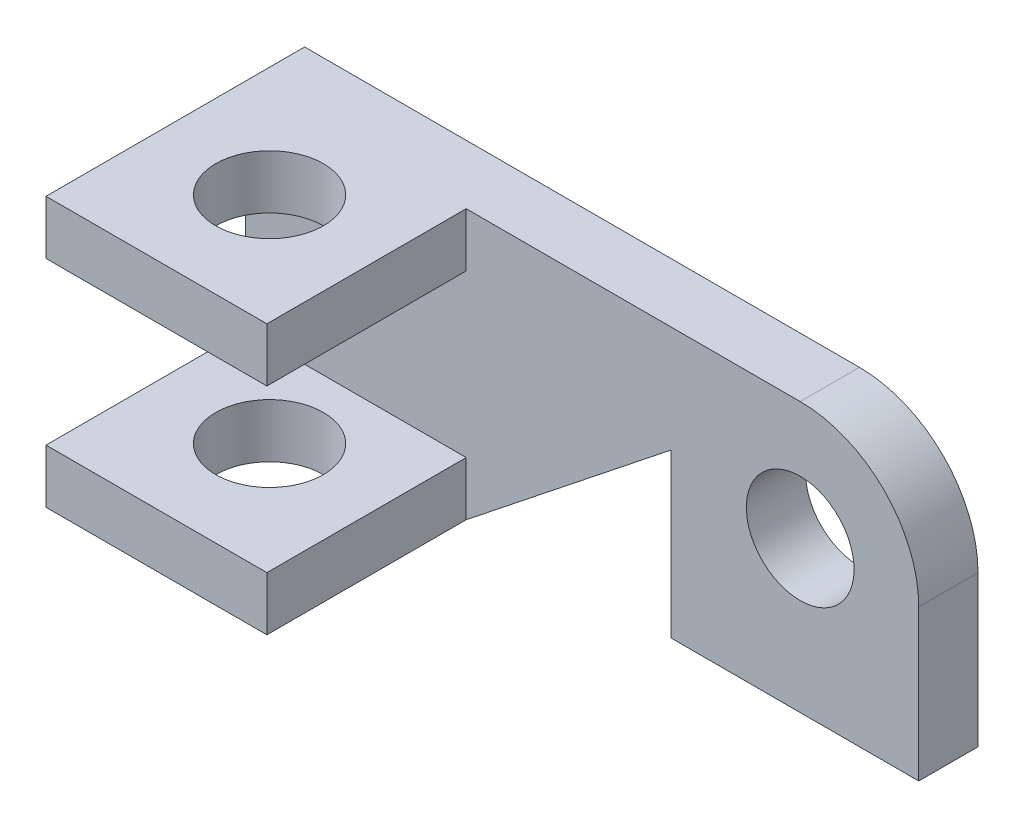
SolidWorks part; units mm, degrees
ref_plane "Front Plane" through (0, 0, 0) normal (0, 0, 1) x (1, 0, 0)
ref_plane "Top Plane" through (0, 0, 0) normal (0, 1, 0) x (1, 0, 0)
ref_plane "Right Plane" through (0, 0, 0) normal (1, 0, 0) x (0, 0, -1)
sketch "Sketch1" plane through (0, 0, 0) normal (0, 0, 1) x (1, 0, 0)
  line L0 (0, 0) -> (41000, 0)
  line L1 (41000, 0) -> (79000, 30197.4198)
  line L2 (79000, 30197.4198) -> (79000, 0)
  line L3 (79000, 0) -> (125000, 0)
  line L4 (125000, 0) -> (125000, 28000)
  line L5 (103000, 50000) -> (0, 50000)
  line L6 (0, 50000) -> (0, 0)
  circle A0 centre (103000, 28000) radius 10000
  arc A1 (103000, 50000) -> (125000, 28000) centre (103000, 28000) cw
  point P7 (79000, 30197.4198)
  dimension "D7" = 20000
  dimension "D2" = 22000
  dimension "D1" = 50000
  dimension "D3" = 46000
  dimension "D4" = 30197.4198
  dimension "D5" = 41000
  dimension "D6" = 28000
  dimension "D8" = 22000
  dimension "D9" = 22000
  dimension "D10" = 125000
extrude "Boss-Extrude1" add sketch "Sketch1" along normal blind 11000 contours L4 A1 L5 L6 L0 L1 L2 L3
extrude "Cut-Extrude1" cut sketch "Sketch1<5>" along normal through all contours A0
sketch "Sketch1<5>" plane through (0, 0, 0) normal (0, 0, 1) x (1, 0, 0) same geometry as "Sketch1"
sketch "Sketch2" plane through (0, 0, 11000) normal (0, 0, 1) x (1, 0, 0)
  line L0 (0, 10000) -> (0, 0)
  line L1 (0, 50000) -> (41000, 50000)
  line L2 (0, 50000) -> (0, 40000)
  line L3 (0, 40000) -> (41000, 40000)
  line L4 (41000, 50000) -> (41000, 40000)
  line L5 (0, 10000) -> (41000, 10000)
  line L6 (41000, 10000) -> (41000, 0)
  line L7 (0, 0) -> (41000, 0)
  dimension "D1" = 10000
  dimension "D2" = 41000
  dimension "D3" = 2
extrude "Boss-Extrude5" add sketch "Sketch2" along normal blind 37000
sketch "Sketch3" plane through (0, 0, 0) normal (0, -1, 0) x (1, 0, 0)
  line L0 (0, 48000) -> (0, 0) construction
  line L1 (0, 48000) -> (41000, 48000) construction
  circle A0 centre (20500, 27000) radius 10000
  dimension "D1" = 20000
  dimension "D2" = 20500
  dimension "D3" = 21000
extrude "Cut-Extrude2" cut sketch "Sketch3" against normal through all contours A0
